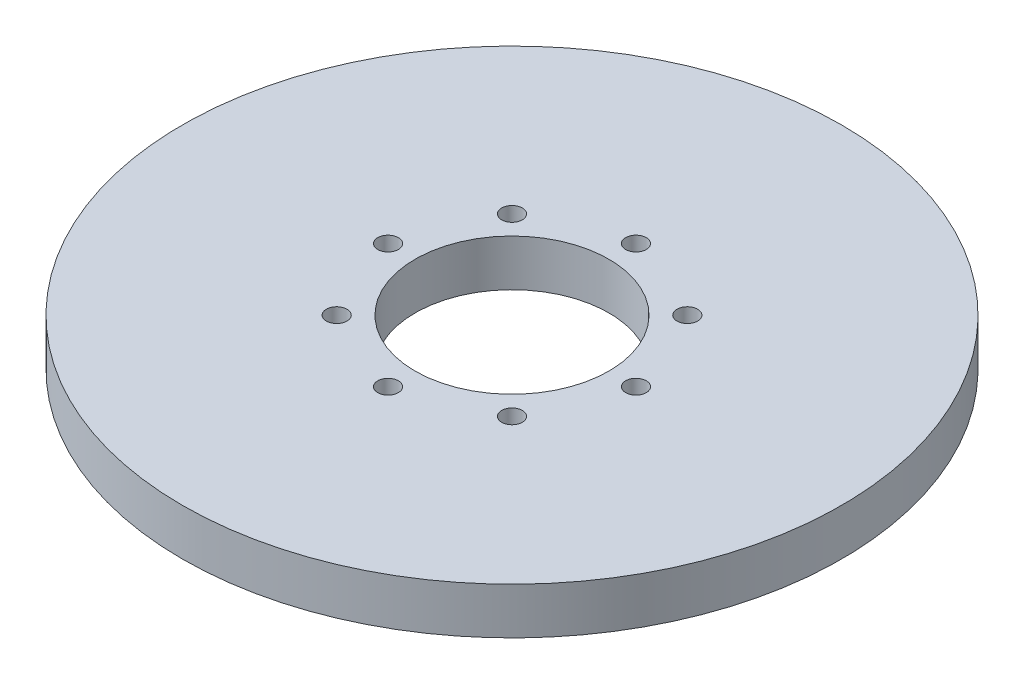
SolidWorks part; units mm, degrees
ref_plane "Front Plane" through (0, 0, 0) normal (0, 0, 1) x (1, 0, 0)
ref_plane "Top Plane" through (0, 0, 0) normal (0, 1, 0) x (1, 0, 0)
ref_plane "Right Plane" through (0, 0, 0) normal (1, 0, 0) x (0, 0, -1)
sketch "Sketch1" plane through (0, 0, 0) normal (0, 1, 0) x (1, 0, 0)
  circle A0 centre (0, 0) radius 85
  dimension "FLANGE_OD" = 170
extrude "Boss-Extrude1" add sketch "Sketch1" along normal blind 12
sketch "Sketch2" plane through (0, 0, 0) normal (0, 1, 0) x (1, 0, 0)
  circle A0 centre (0, 0) radius 25
  dimension "BORE_D" = 50
extrude "Cut-Extrude1" cut sketch "Sketch2" along normal through all
sketch "Sketch3" plane through (0, 12, 0) normal (0, 1, 0) x (1, 0, 0)
  circle A0 centre (0, 0) radius 31.9736 construction
  circle A1 centre (-31.9736, 0) radius 2.6613
  dimension "BOLT_D" = 5.3226
  dimension "BOLT_PCD" = 63.9473
extrude "Cut-Extrude2" cut sketch "Sketch3" against normal blind 11.7309
pattern_circular "CirPattern1" count 8 over 360 about axis through (0, 0, 0) along (0, 1, 0) of "Cut-Extrude2"
